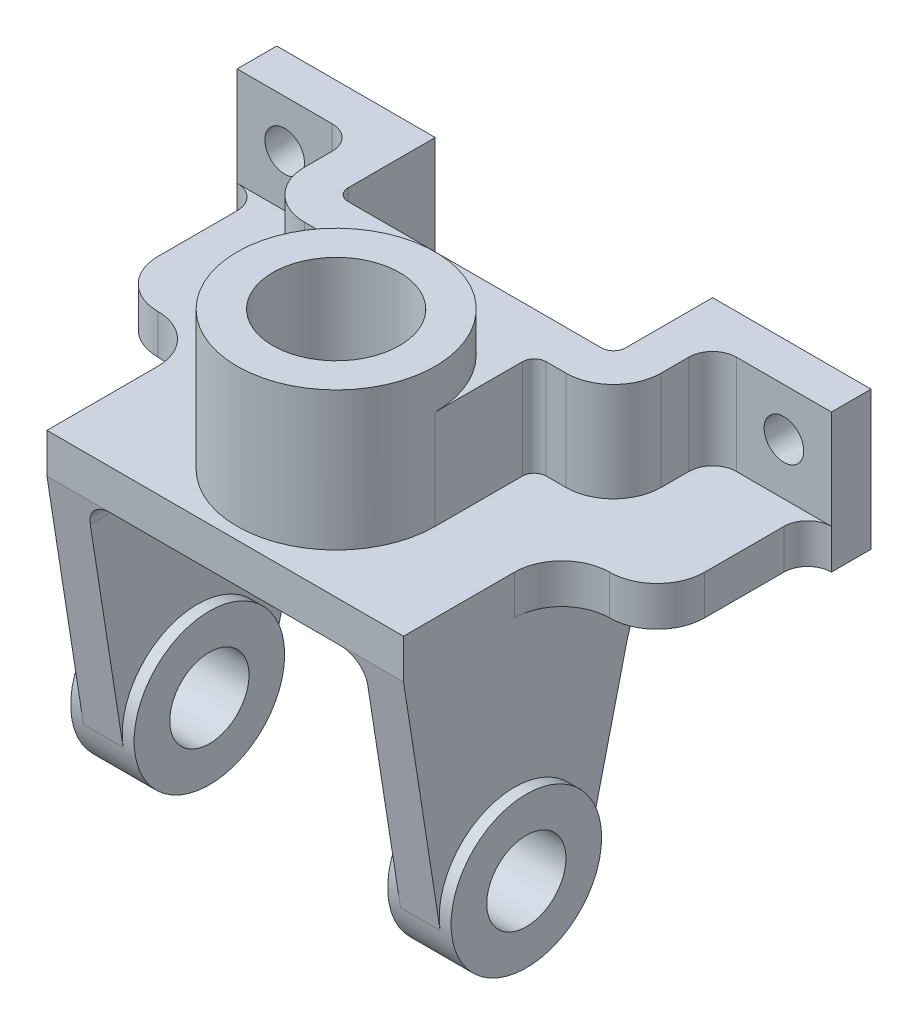
SolidWorks part; units mm, degrees
ref_plane "前视基准面" through (0, 0, 0) normal (0, 0, 1) x (1, 0, 0)
ref_plane "上视基准面" through (0, 0, 0) normal (0, 1, 0) x (1, 0, 0)
ref_plane "右视基准面" through (0, 0, 0) normal (1, 0, 0) x (0, 0, -1)
other "Configuration Table"
sketch3d "3D草图1"
  line L0 (0, 0, 0) -> (0, 10, 0)
ref_plane "基准面1" through (0, 0, 0) normal (0, 1, 0) x (1, 0, 0)
sketch "草图1" plane through (0, 0, 0) normal (0, 1, 0) x (1, 0, 0)
  line L0 (-75, 50) -> (-75, 60)
  line L1 (-75, 60) -> (-35, 60)
  line L2 (-35, 60) -> (-35, 38)
  line L3 (-32, 35) -> (32, 35)
  line L4 (35, 38) -> (35, 60)
  line L5 (35, 60) -> (75, 60)
  line L6 (75, 60) -> (75, 50)
  line L7 (69, 44) -> (69, 24)
  line L8 (45, 0) -> (45, -28)
  line L9 (45, -28) -> (-45, -28)
  line L10 (-45, -28) -> (-45, 0)
  line L11 (-69, 24) -> (-69, 44)
  arc A0 (-35, 38) -> (-32, 35) centre (-32, 38) ccw
  arc A1 (32, 35) -> (35, 38) centre (32, 38) ccw
  arc A2 (75, 50) -> (69, 44) centre (75, 44) ccw
  arc A3 (69, 24) -> (57, 12) centre (57, 24) cw
  arc A4 (57, 12) -> (45, 0) centre (57, 0) ccw
  arc A5 (-45, 0) -> (-57, 12) centre (-57, 0) ccw
  arc A6 (-57, 12) -> (-69, 24) centre (-57, 24) cw
  arc A7 (-69, 44) -> (-75, 50) centre (-75, 44) ccw
extrude "凸台-拉伸1" add sketch "草图1" along normal blind 10
sketch3d "3D草图2"
  line L0 (0, 10, 0) -> (0, 20, 0)
ref_plane "基准面2" through (0, 10, 0) normal (0, 1, 0) x (1, 0, 0)
sketch "草图2" plane through (0, 10, 0) normal (0, 1, 0) x (1, 0, 0)
  line L0 (-75, 50) -> (-75, 60)
  line L1 (-75, 60) -> (-35, 60)
  line L2 (-35, 60) -> (-35, 38)
  line L3 (-32, 35) -> (32, 35)
  line L4 (35, 38) -> (35, 60)
  line L5 (35, 60) -> (75, 60)
  line L6 (75, 60) -> (75, 50)
  line L7 (75, 50) -> (51, 50)
  line L8 (45, 44) -> (45, 37)
  line L9 (33, 25) -> (28, 25)
  line L10 (25, 22) -> (25, 0)
  line L11 (25, 0) -> (-25, 0)
  line L12 (-25, 0) -> (-25, 22)
  line L13 (-28, 25) -> (-33, 25)
  line L14 (-45, 37) -> (-45, 44)
  line L15 (-51, 50) -> (-75, 50)
  arc A0 (-35, 38) -> (-32, 35) centre (-32, 38) ccw
  arc A1 (32, 35) -> (35, 38) centre (32, 38) ccw
  arc A2 (51, 50) -> (45, 44) centre (51, 44) ccw
  arc A3 (45, 37) -> (33, 25) centre (33, 37) cw
  arc A4 (28, 25) -> (25, 22) centre (28, 22) ccw
  arc A5 (-25, 22) -> (-28, 25) centre (-28, 22) ccw
  arc A6 (-33, 25) -> (-45, 37) centre (-33, 37) cw
  arc A7 (-45, 44) -> (-51, 50) centre (-51, 44) ccw
extrude "凸台-拉伸2" add sketch "草图2" along normal blind 25
sketch3d "3D草图3"
  line L0 (0, 10, 0) -> (0, 20, 0)
ref_plane "基准面3" through (0, 10, 0) normal (0, 1, 0) x (1, 0, 0)
sketch "草图3" plane through (0, 10, 0) normal (0, 1, 0) x (1, 0, 0)
  arc A0 (25, 0) -> (-25, 0) centre (0, 0) ccw
  arc A1 (-25, 0) -> (25, 0) centre (0, 0) ccw
extrude "凸台-拉伸3" add sketch "草图3" along normal blind 35
sketch3d "3D草图4"
  line L0 (-40, 0, 0) -> (-30, 0, 0)
ref_plane "基准面4" through (-40, 0, 0) normal (1, 0, 0) x (0, 0, -1)
sketch "草图4" plane through (-40, 0, 0) normal (1, 0, 0) x (0, 0, -1)
  line L0 (-28, 0) -> (52.7034, 0)
  line L1 (28.3956, -19.1579) -> (18.4739, -60.44)
  line L2 (18.4739, -60.44) -> (-18.7713, -58.9392)
  line L3 (-18.7713, -58.9392) -> (-28, 0)
  arc A0 (52.7034, 0) -> (28.3956, -19.1579) centre (52.7034, -25) ccw
extrude "凸台-拉伸6" add sketch "草图4" along normal mid plane 10
sketch3d "3D草图5"
  line L0 (-40, -56, 0) -> (-30, -56, 0)
ref_plane "基准面5" through (-40, -56, 0) normal (1, 0, 0) x (0, 0, -1)
sketch "草图5" plane through (-40, -56, 0) normal (1, 0, 0) x (0, 0, -1)
  arc A0 (19, 0) -> (-19, 0) centre (0, 0) ccw
  arc A1 (-19, 0) -> (19, 0) centre (0, 0) ccw
extrude "凸台-拉伸7" add sketch "草图5" along normal mid plane 16
sketch3d "3D草图6"
  line L0 (40, 0, 0) -> (50, 0, 0)
ref_plane "基准面6" through (40, 0, 0) normal (1, 0, 0) x (0, 0, -1)
sketch "草图6" plane through (40, 0, 0) normal (1, 0, 0) x (0, 0, -1)
  line L0 (-28, 0) -> (52.7034, 0)
  line L1 (28.3956, -19.1579) -> (18.4739, -60.44)
  line L2 (18.4739, -60.44) -> (-18.7713, -58.9392)
  line L3 (-18.7713, -58.9392) -> (-28, 0)
  arc A0 (52.7034, 0) -> (28.3956, -19.1579) centre (52.7034, -25) ccw
extrude "凸台-拉伸8" add sketch "草图6" along normal mid plane 10
sketch3d "3D草图7"
  line L0 (40, -56, 0) -> (50, -56, 0)
ref_plane "基准面7" through (40, -56, 0) normal (1, 0, 0) x (0, 0, -1)
sketch "草图7" plane through (40, -56, 0) normal (1, 0, 0) x (0, 0, -1)
  arc A0 (19, 0) -> (-19, 0) centre (0, 0) ccw
  arc A1 (-19, 0) -> (19, 0) centre (0, 0) ccw
extrude "凸台-拉伸9" add sketch "草图7" along normal mid plane 16
sketch3d "3D草图8"
  line L0 (0, 0, 0) -> (0, 10, 0)
ref_plane "基准面8" through (0, 0, 0) normal (0, 1, 0) x (1, 0, 0)
sketch "草图8" plane through (0, 0, 0) normal (0, 1, 0) x (1, 0, 0)
  arc A0 (16, 0) -> (-16, 0) centre (0, 0) ccw
  arc A1 (-16, 0) -> (16, 0) centre (0, 0) ccw
extrude "切除-拉伸1" cut sketch "草图8" against normal through all and the other way through all
sketch3d "3D草图9"
  line L0 (0, -56, 0) -> (10, -56, 0)
ref_plane "基准面9" through (0, -56, 0) normal (1, 0, 0) x (0, 0, -1)
sketch "草图9" plane through (0, -56, 0) normal (1, 0, 0) x (0, 0, -1)
  arc A0 (10, 0) -> (-10, 0) centre (0, 0) ccw
  arc A1 (-10, 0) -> (10, 0) centre (0, 0) ccw
extrude "切除-拉伸2" cut sketch "草图9" against normal through all and the other way through all
sketch3d "3D草图10"
  line L0 (-63, 23, 0) -> (-63, 23, 10)
ref_plane "基准面10" through (-63, 23, 0) normal (0, 0, 1) x (1, 0, 0)
sketch "草图10" plane through (-63, 23, 0) normal (0, 0, 1) x (1, 0, 0)
  arc A0 (5, 0) -> (-5, 0) centre (0, 0) ccw
  arc A1 (-5, 0) -> (5, 0) centre (0, 0) ccw
extrude "切除-拉伸3" cut sketch "草图10" against normal through all and the other way through all
sketch3d "3D草图11"
  line L0 (63, 23, 0) -> (63, 23, 10)
ref_plane "基准面11" through (63, 23, 0) normal (0, 0, 1) x (1, 0, 0)
sketch "草图11" plane through (63, 23, 0) normal (0, 0, 1) x (1, 0, 0)
  arc A0 (5, 0) -> (-5, 0) centre (0, 0) ccw
  arc A1 (-5, 0) -> (5, 0) centre (0, 0) ccw
extrude "切除-拉伸4" cut sketch "草图11" against normal through all and the other way through all
fillet "圆角1" radius 6 2 edges at (35, 0, -5) (-35, 0, -5) tangent propagation no
